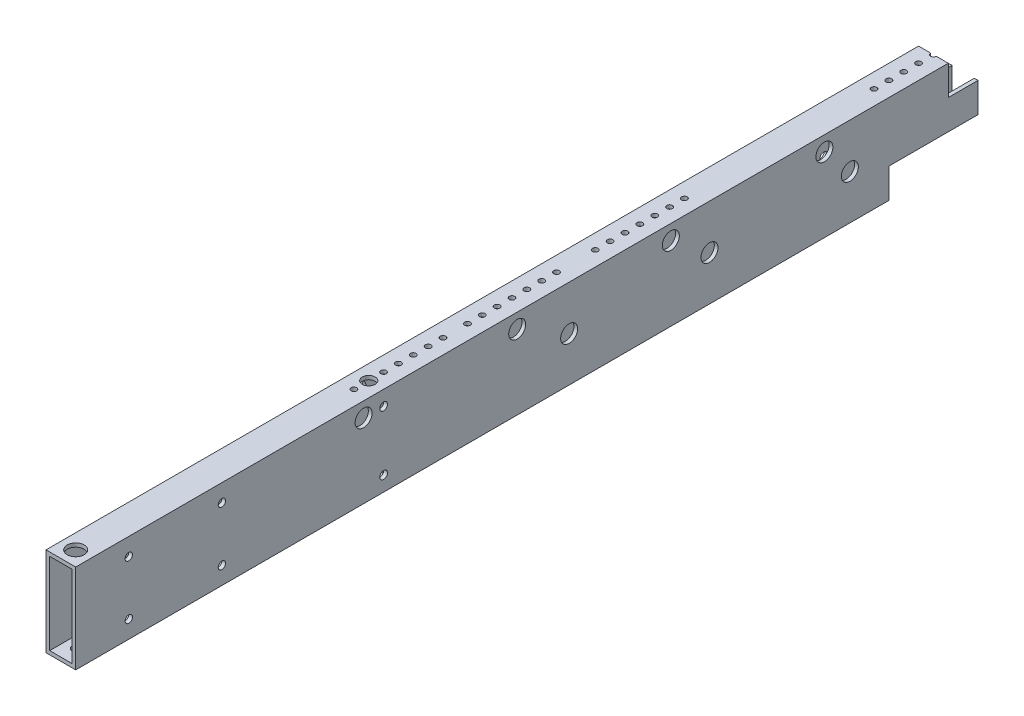
SolidWorks part; units mm, degrees
ref_plane "Front Plane" through (0, 0, 0) normal (0, 0, 1) x (1, 0, 0)
ref_plane "Top Plane" through (0, 0, 0) normal (0, 1, 0) x (1, 0, 0)
ref_plane "Right Plane" through (0, 0, 0) normal (1, 0, 0) x (0, 0, -1)
sketch "Sketch1" plane through (0, 0, 0) normal (0, 0, 1) x (1, 0, 0)
  line L1 (-12.7, -38.1) -> (12.7, -38.1)
  line L2 (-12.7, -38.1) -> (-12.7, 38.1)
  line L3 (-12.7, 38.1) -> (12.7, 38.1)
  line L4 (12.7, -38.1) -> (12.7, 38.1)
  line L5 (-12.7, -38.1) -> (12.7, 38.1) construction
  line L6 (-12.7, 38.1) -> (12.7, -38.1) construction
  point P0 (0, 0)
  dimension "D1" = 25.4
  dimension "D2" = 76.2
extrude "Boss-Extrude1" add sketch "Sketch1" along normal mid plane 771.398
shell "Shell1" thickness 3.175 removed face at (0, 0, -385.699) removed face at (0, 0, 385.699)
sketch "Sketch2" plane through (12.7, 0, 0) normal (1, 0, 0) x (0, 0, -1)
  line L1 (385.699, -38.1) -> (309.499, -38.1)
  line L2 (385.699, -38.1) -> (385.699, -12.7)
  line L3 (385.699, -12.7) -> (309.499, -12.7)
  line L4 (309.499, -38.1) -> (309.499, -12.7)
  dimension "D1" = 25.4
  dimension "D2" = 76.2
extrude "Cut-Extrude1" cut sketch "Sketch2" against normal through all
sketch "Sketch3" plane through (12.7, 0, 0) normal (1, 0, 0) x (0, 0, -1)
  line L1 (385.699, 38.1) -> (360.299, 38.1)
  line L2 (385.699, 38.1) -> (385.699, 12.7)
  line L3 (385.699, 12.7) -> (360.299, 12.7)
  line L4 (360.299, 38.1) -> (360.299, 12.7)
  dimension "D1" = 25.4
extrude "Cut-Extrude2" cut sketch "Sketch3" against normal through all
sketch "Sketch4" plane through (0, 38.1, 0) normal (0, 1, 0) x (1, 0, 0)
  line L0 (-12.7, 360.299) -> (12.7, 360.299) construction
  circle A0 centre (0, 147.3945) radius 2.3812
  circle A1 centre (0, 134.6945) radius 2.3812
  circle A2 centre (0, 121.9945) radius 2.3812
  circle A3 centre (0, 109.2945) radius 2.3812
  circle A4 centre (0, 96.5945) radius 2.3812
  circle A5 centre (0, 83.8945) radius 2.3812
  circle A6 centre (0, 71.1945) radius 2.3812
  circle A7 centre (0, 38.0987) radius 2.3812
  circle A8 centre (0, 25.3987) radius 2.3813
  circle A9 centre (0, 12.6987) radius 2.3813
  circle A10 centre (0, -0.0013) radius 2.3813
  circle A11 centre (0, -12.7013) radius 2.3812
  circle A12 centre (0, -25.4013) radius 2.3812
  circle A13 centre (0, -38.1013) radius 2.3812
  circle A15 centre (0, -58.9932) radius 2.3812
  circle A16 centre (0, -71.6932) radius 2.3812
  circle A17 centre (0, -84.3932) radius 2.3812
  circle A18 centre (0, -97.0932) radius 2.3812
  circle A19 centre (0, -109.7932) radius 2.3812
  circle A20 centre (0, -122.4932) radius 2.3812
  circle A21 centre (0, -135.1932) radius 2.3813
  point P33 (0, 360.299)
  dimension "D1" = 4.7625
  dimension "D3" = 12.7
  dimension "D4" = 12.7
  dimension "D5" = 12.7
  dimension "D6" = 12.7
  dimension "D7" = 12.7
  dimension "D8" = 12.7
  dimension "D9" = 322.2003
  dimension "D10" = 12.7
  dimension "D11" = 12.7
  dimension "D12" = 12.7
  dimension "D13" = 12.7
  dimension "D14" = 12.7
  dimension "D15" = 12.7
  dimension "D16" = 12.7
  dimension "D17" = 419.2922
  dimension "D18" = 12.7
  dimension "D19" = 12.7
  dimension "D20" = 12.7
  dimension "D21" = 12.7
  dimension "D22" = 12.7
  dimension "D2" = 212.9045
extrude "Cut-Extrude3" cut sketch "Sketch4" against normal through all
sketch "Sketch5" plane through (0, 38.1, 0) normal (0, 1, 0) x (1, 0, 0)
  line L0 (-12.7, 360.299) -> (12.7, 360.299) construction
  circle A0 centre (0, 360.299) radius 2.3813
  circle A1 centre (0, 347.599) radius 2.3813
  circle A2 centre (0, 334.899) radius 2.3813
  circle A3 centre (0, 322.199) radius 2.3813
  circle A4 centre (0, 309.499) radius 2.3813
  dimension "D1" = 4.7625
  dimension "D3" = 12.7
  dimension "D4" = 12.7
  dimension "D5" = 12.7
  dimension "D8" = 0
  dimension "D2" = 12.7
extrude "Cut-Extrude4" cut sketch "Sketch5" against normal up to next
sketch "Sketch6" plane through (0, -38.1, 0) normal (0, -1, 0) x (1, 0, 0)
  line L0 (-12.7, -309.499) -> (12.7, -309.499) construction
  circle A0 centre (0, -309.499) radius 2.3813
  circle A1 centre (0, -296.799) radius 2.3813
  circle A2 centre (0, -284.099) radius 2.3813
  circle A3 centre (0, -258.699) radius 2.3813
  circle A6 centre (0, -271.399) radius 2.3813
  dimension "D1" = 4.7625
  dimension "D2" = 12.7
  dimension "D3" = 12.7
  dimension "D4" = 12.7
  dimension "D5" = 12.7
  dimension "D6" = 0
extrude "Cut-Extrude5" cut sketch "Sketch6" against normal up to next
sketch3d "3DSketch1" [suppressed]
  line L0 (0, 34.925, -109.2945) -> (0, 38.1, -109.2945) construction
  line L1 (0, 34.925, 97.0932) -> (0, 38.1, 97.0932) construction
  point P0 (0, 38.1, -109.2945)
  point P1 (0, 0, 0)
  point P4 (0, 38.1, 97.0932)
sketch "Sketch11" plane through (12.7, 0, 0) normal (1, 0, 0) x (0, 0, -1)
  point P0 (-340.3244, 23.1254)
  point P1 (-260.7244, 23.1254)
  point P3 (-260.7244, -23.1)
  point P5 (-340.3244, -23.1)
hole_wizard "CBORE for M6 Hex Head Bolt1" positions "Sketch19" profile "Sketch18" counterbore size "M6" standard "Lanco STD" end condition through all
sketch "Sketch19" plane through (-12.7, 0, 0) normal (-1, 0, 0) x (0, 0, 1)
  point P0 (260.7244, 23.1254)
  point P3 (260.7244, -23.1)
  point P6 (340.3244, 23.1254)
  point P9 (340.3244, -23.1)
sketch "Sketch18" plane through (-12.7, 23.1254, 260.7244) normal (0, 1, 0) x (0, 0, 1)
  line L0 (0, 0) -> (0, 25.4)
  line L1 (0, 25.4) -> (3.15, 25.4)
  line L3 (3.15, 25.4) -> (3.15, 4)
  line L4 (3.15, 4) -> (7.2735, 4)
  line L5 (7.2735, 4) -> (7.2735, 0)
  line L7 (7.2735, 0) -> (0, 0)
  line L11 (0, -6.35) -> (0, 107.95) construction
  dimension "Thru Hole Dia." = 6.3
  dimension "Thru Hole Depth" = 25.4
  dimension "C'Bore Dia." = 14.547
  dimension "C'Bore Depth" = 4
hole_wizard "CBORE for M6 Hex Head Cap Screw1" positions "Sketch21" profile "Sketch20" counterbore size "M6" standard "ANSI Metric" end condition through all
sketch "Sketch21" plane through (-12.7, 0, 0) normal (-1, 0, 0) x (0, 0, 1)
  line L0 (385.699, 38.1) -> (-360.299, 38.1) construction
  line L1 (385.699, 38.1) -> (385.699, -38.1) construction
  point P0 (122.4678, 25.4)
  point P2 (122.4678, -25.4)
  dimension "D1" = 12.7
  dimension "D2" = 63.5
  dimension "D3" = 263.2312
  dimension "D4" = 263.2312
sketch "Sketch20" plane through (-12.7, 25.4, 122.4678) normal (0, 1, 0) x (0, 0, 1)
  line L0 (0, 0) -> (0, 25.4)
  line L1 (0, 25.4) -> (3.3, 25.4)
  line L3 (3.3, 25.4) -> (3.3, 4.15)
  line L4 (3.3, 4.15) -> (7.275, 4.15)
  line L5 (7.275, 4.15) -> (7.275, 0)
  line L7 (7.275, 0) -> (0, 0)
  line L11 (0, -6.35) -> (0, 107.95) construction
  dimension "Thru Hole Dia." = 6.6
  dimension "Thru Hole Depth" = 25.4
  dimension "C'Bore Dia." = 14.55
  dimension "C'Bore Depth" = 4.15
hole_wizard "CBORE for M6 Hex Head Cap Screw2" positions "Sketch26" profile "Sketch25" counterbore size "M6" standard "ANSI Metric" end condition through all
sketch "Sketch26" plane through (0, 38.1, 0) normal (0, 1, 0) x (1, 0, 0)
  line L0 (12.7, -385.699) -> (-12.7, -385.699) construction
  point P0 (0, -372.999)
  dimension "D1" = 12.7
sketch "Sketch25" plane through (0, 38.1, 372.999) normal (1, 0, 0) x (0, 0, 1)
  line L0 (0, 0) -> (0, 76.2)
  line L1 (0, 76.2) -> (3.3, 76.2)
  line L3 (3.3, 76.2) -> (3.3, 4.15)
  line L4 (3.3, 4.15) -> (7.275, 4.15)
  line L5 (7.275, 4.15) -> (7.275, 0)
  line L7 (7.275, 0) -> (0, 0)
  line L11 (0, -6.35) -> (0, 107.95) construction
  dimension "Thru Hole Dia." = 6.6
  dimension "Thru Hole Depth" = 76.2
  dimension "C'Bore Dia." = 14.55
  dimension "C'Bore Depth" = 4.15
hole_wizard "CBORE for M6 Hex Head Cap Screw3" positions "Sketch28" profile "Sketch27" counterbore size "M6" standard "ANSI Metric" end condition through all
sketch "Sketch28" plane through (12.7, 0, 0) normal (1, 0, 0) x (0, 0, -1)
  point P9 (36.1449, 0)
  point P13 (156.1449, 0)
  point P15 (276.1449, 0)
sketch "Sketch27" plane through (12.7, 0, -36.1449) normal (0, 1, 0) x (0, 0, -1)
  line L0 (0, 0) -> (0, 25.4)
  line L1 (0, 25.4) -> (3.3, 25.4)
  line L3 (3.3, 25.4) -> (3.3, 4.15)
  line L4 (3.3, 4.15) -> (7.275, 4.15)
  line L5 (7.275, 4.15) -> (7.275, 0)
  line L7 (7.275, 0) -> (0, 0)
  line L11 (0, -6.35) -> (0, 107.95) construction
  dimension "Thru Hole Dia." = 6.6
  dimension "Thru Hole Depth" = 25.4
  dimension "C'Bore Dia." = 14.55
  dimension "C'Bore Depth" = 4.15
hole_wizard "CBORE for M6 Hex Head Bolt2" positions "Sketch32" profile "Sketch31" counterbore size "M6" standard "DIN" end condition through all
sketch "Sketch32" plane through (12.7, 0, 0) normal (1, 0, 0) x (0, 0, -1)
  line L0 (-385.699, 38.1) -> (360.299, 38.1) construction
  line L2 (385.699, -12.7) -> (385.699, 12.7) construction
  point P0 (254.381, 25.4)
  point P2 (123.063, 25.4)
  point P4 (-8.255, 25.4)
  point P6 (-139.573, 25.4)
  point P15 (385.699, 0)
  dimension "D1" = 12.7
  dimension "D2" = 131.318
  dimension "D3" = 131.318
  dimension "D4" = 131.318
  dimension "D5" = 131.318
sketch "Sketch31" plane through (12.7, 25.4, -254.381) normal (0, 1, 0) x (0, 0, -1)
  line L0 (0, 0) -> (0, 25.4)
  line L1 (0, 25.4) -> (3.15, 25.4)
  line L3 (3.15, 25.4) -> (3.15, 4)
  line L4 (3.15, 4) -> (7.2735, 4)
  line L5 (7.2735, 4) -> (7.2735, 0)
  line L7 (7.2735, 0) -> (0, 0)
  line L11 (0, -6.35) -> (0, 107.95) construction
  dimension "Thru Hole Dia." = 6.3
  dimension "Thru Hole Depth" = 25.4
  dimension "C'Bore Dia." = 14.547
  dimension "C'Bore Depth" = 4
hole_wizard "CBORE for M6 Hex Socket Head Cap Screw1" positions "Sketch34" profile "Sketch33" counterbore size "M6" standard "Lanco STD" end condition through all
sketch "Sketch34" plane through (0, 38.1, 0) normal (0, 1, 0) x (1, 0, 0)
  point P0 (0, -122.4932)
sketch "Sketch33" plane through (0, 38.1, 122.4932) normal (1, 0, 0) x (0, 0, 1)
  line L0 (0, 0) -> (0, 76.2)
  line L1 (0, 76.2) -> (3.2, 76.2)
  line L3 (3.2, 76.2) -> (3.2, 7)
  line L4 (3.2, 7) -> (5.5, 7)
  line L5 (5.5, 7) -> (5.5, 0)
  line L7 (5.5, 0) -> (0, 0)
  line L11 (0, -6.35) -> (0, 107.95) construction
  dimension "Thru Hole Dia." = 6.4
  dimension "Thru Hole Depth" = 76.2
  dimension "C'Bore Dia." = 11
  dimension "C'Bore Depth" = 7
equation "\"5.1`7\"=2.30417"
